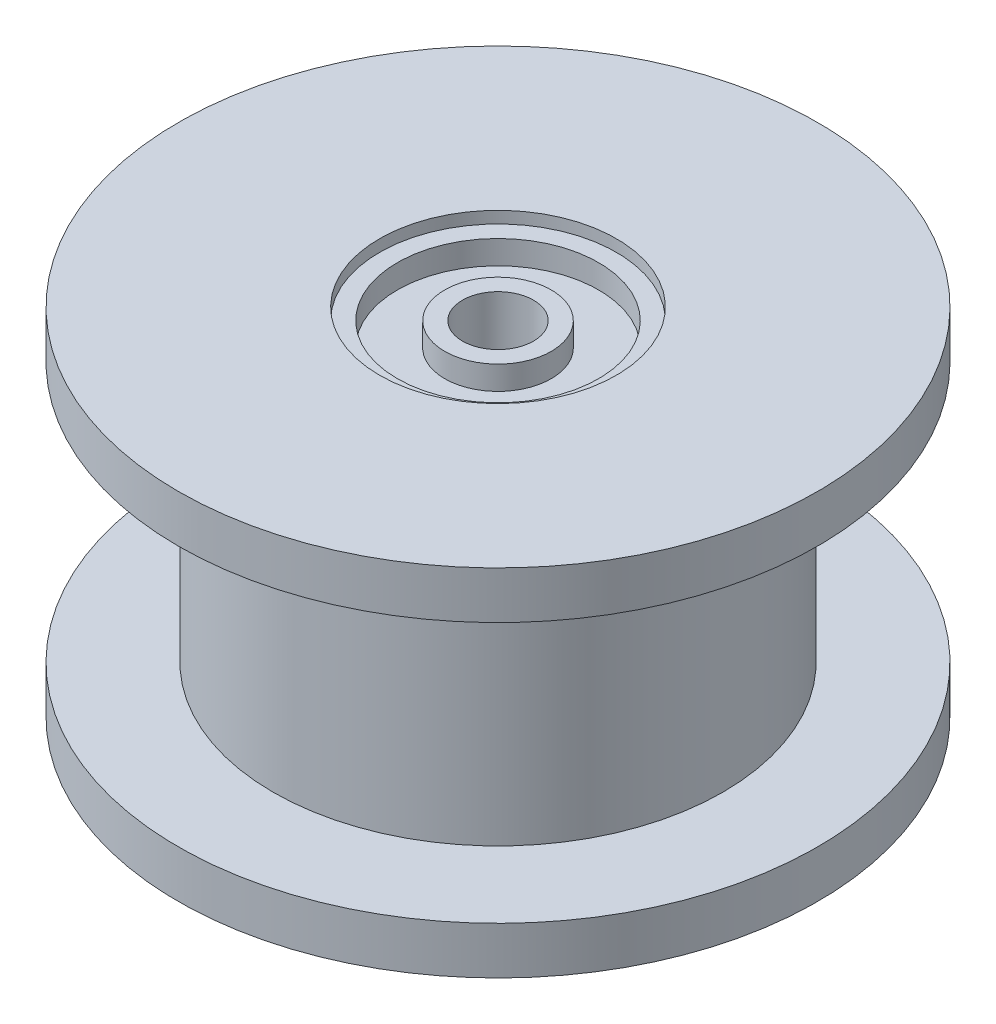
SolidWorks part; units mm, degrees
ref_plane "前视基准面" through (0, 0, 0) normal (0, 0, 1) x (1, 0, 0)
ref_plane "上视基准面" through (0, 0, 0) normal (0, 1, 0) x (1, 0, 0)
ref_plane "右视基准面" through (0, 0, 0) normal (1, 0, 0) x (0, 0, -1)
sketch "草图1" plane through (0, 0, 0) normal (0, 1, 0) x (1, 0, 0)
  circle A0 centre (0, 0) radius 9.5
  dimension "D1" = 19
extrude "凸台-拉伸1" add sketch "草图1" along normal blind 11
sketch "草图2" plane through (0, 11, 0) normal (0, 1, 0) x (1, 0, 0)
  circle A0 centre (0, 0) radius 13.5
  dimension "D1" = 27
extrude "凸台-拉伸2" add sketch "草图2" along normal blind 2
sketch "草图3" plane through (0, 0, 0) normal (0, -1, 0) x (1, 0, 0)
  circle A0 centre (0, 0) radius 13.5
  dimension "D1" = 27
extrude "凸台-拉伸3" add sketch "草图3" along normal blind 2
sketch "草图4" plane through (0, -2, 0) normal (0, -1, 0) x (1, 0, 0)
  circle A0 centre (0, 0) radius 5
  circle A1 centre (0, 0) radius 1.5
  circle A2 centre (0, 0) radius 2.25
  circle A3 centre (0, 0) radius 4.25
  dimension "D1" = 10
  dimension "D2" = 3
  dimension "D3" = 4.5
  dimension "D4" = 8.5
extrude "切除-拉伸1" cut sketch "草图4" against normal blind 0.5 contours A0 | A3
extrude "切除-拉伸2" cut sketch "草图4<3>" against normal blind 1.5 contours A3 A2 region at (-4.1298, -2, 0)
sketch "草图4<3>" plane through (0, -2, 0) normal (0, -1, 0) x (1, 0, 0) same geometry as "草图4"
extrude "切除-拉伸3" cut sketch "草图4<4>" against normal blind 0.5 contours A2 A1 region at (-2.1864, -2, 0)
sketch "草图4<4>" plane through (0, -2, 0) normal (0, -1, 0) x (1, 0, 0) same geometry as "草图4"
extrude "切除-拉伸4" cut sketch "草图4<5>" against normal through all contours A1 region at (0, -2, 0)
sketch "草图4<5>" plane through (0, -2, 0) normal (0, -1, 0) x (1, 0, 0) same geometry as "草图4"
sketch "草图6" plane through (0, 13, 0) normal (0, 1, 0) x (1, 0, 0)
  circle A0 centre (0, 0) radius 1.5
  circle A1 centre (0, 0) radius 2.25
  circle A2 centre (0, 0) radius 4.25
  circle A3 centre (0, 0) radius 5
  circle M1 centre (0, 0) radius 1.5
  dimension "D1" = 3
  dimension "D2" = 4.5
  dimension "D3" = 10
  dimension "D4" = 8.5
extrude "切除-拉伸5" cut sketch "草图6" against normal blind 0.5 contours A3 A2 region at (-4.8586, 13, 0)
extrude "切除-拉伸6" cut sketch "草图6<3>" against normal blind 1.5 contours A2 A1 region at (-4.1298, 13, 0)
sketch "草图6<3>" plane through (0, 13, 0) normal (0, 1, 0) x (1, 0, 0) same geometry as "草图6"
extrude "切除-拉伸7" cut sketch "草图6<4>" against normal blind 0.5 contours A1 M1 region at (-2.1864, 13, 0)
sketch "草图6<4>" plane through (0, 13, 0) normal (0, 1, 0) x (1, 0, 0) same geometry as "草图6"
